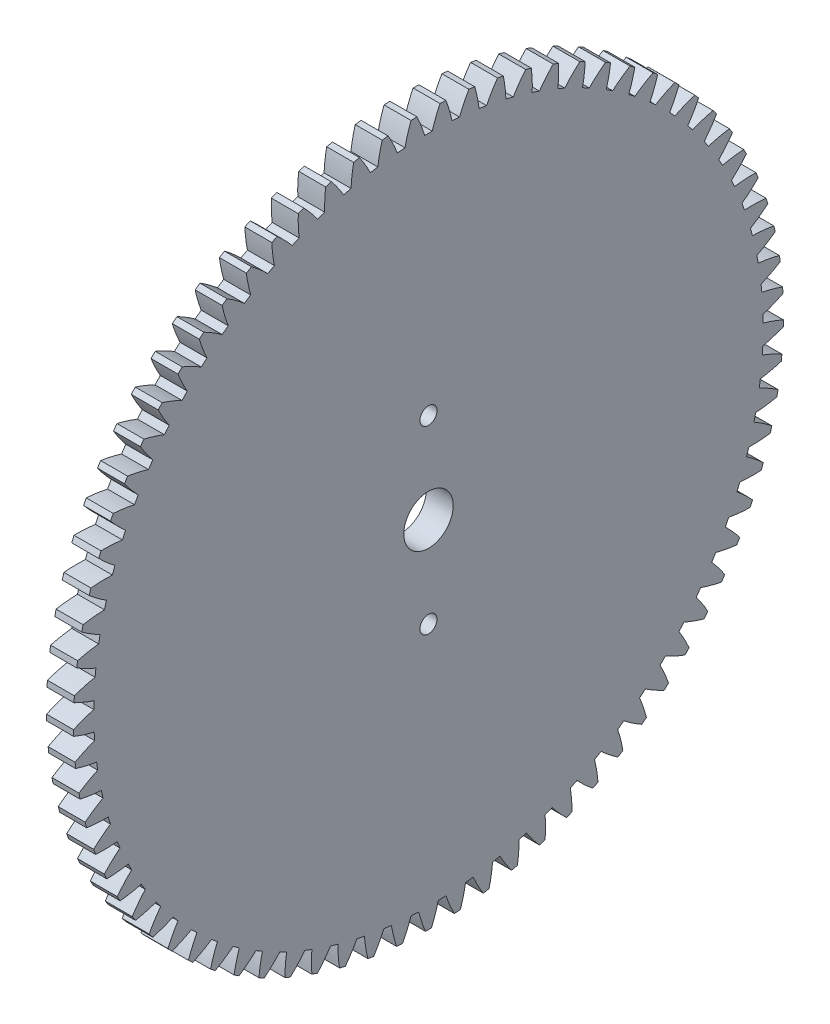
SolidWorks part; units mm, degrees
ref_plane "Plane1" through (0, 0, 0) normal (0, 0, 1) x (1, 0, 0)
ref_plane "Plane2" through (0, 0, 0) normal (0, 1, 0) x (1, 0, 0)
ref_plane "Plane3" through (0, 0, 0) normal (1, 0, 0) x (0, 0, -1)
sketch "HoldingSke" plane through (0, 0, 0) normal (0, 1, 0) x (1, 0, 0)
  line L0 (0, 0) -> (0.225, -0.9744)
  line L1 (-15, 0) -> (100, 0) construction
  line L2 (0, 0) -> (-2.1039, 2.3779)
  line L3 (0, 0) -> (-11.863, 4.5341)
  line L4 (0, 0) -> (1.9427, 8.4147)
  line L5 (0, 0) -> (-46.8476, -17.4728)
  line L6 (0, 0) -> (-1.6579, -1.1186)
  line L7 (-2.1039, 2.3779) -> (8.6586, 51.2059)
  line L8 (-76.2, 54.61) -> (-76.1, 54.61)
  line L9 (-71.009, 38.7566) -> (-53.1078, 45.2721)
  line L10 (-76.2, 71.12) -> (104.1128, 71.12)
  line L11 (0, 0) -> (-2, 0)
  line L12 (-76.2, 101.6) -> (-76.162, 101.6)
  line L13 (24.9733, 27.94) -> (52.9518, 28.4284)
  line L14 (24.9733, 27.94) -> (24.9743, 27.94)
  line L15 (24.9733, 27.94) -> (100.4006, 29.5858)
  line L16 (-63.627, -1) -> (-12.827, -1)
  circle A0 centre (0, 0) radius 0.5
  circle A1 centre (0, 0) radius 37.249
  circle A2 centre (0, 0) radius 37.5
  circle A3 centre (0, 0) radius 0.5
  dimension "MHD" = 74.498
  dimension "Hub_dia" = 75
  dimension "Bore" = 1
  dimension "MBD" = 1
  dimension "Num_teeth" = 77
  dimension "Pitch" = 1
  dimension "Overall_len" = 50
  dimension "Show_teeth" = 77
  dimension "Thickness" = 2
  dimension "OAL" = 50.0001
  dimension "T_dim" = 0.1
  dimension "Ap" = 20
  dimension "H" = 19.05
  dimension "Pitch_radius" = 180.3128
  dimension "Width" = 2
  dimension "Backlash" = 0.038
  dimension "Addendum_fac" = 1
  dimension "Dedendum_fac" = 1.25
  dimension "Clearance_fac" = 0.25
  dimension "Dedendum_add" = 0.001
  dimension "Module" = 1
sketch "BasProSke" plane through (0, 0, 0) normal (0, 1, 0) x (1, 0, 0)
  line L0 (-10, 0) -> (60, 0) construction
  line L1 (0, 0) -> (0, 39.5)
  line L2 (0, 0) -> (2, 0)
  line L3 (2, 0) -> (2, 39.5)
  line L4 (2, 39.5) -> (0, 39.5)
  dimension "Thickness" = 2
  dimension "Diameter" = 79
revolve "Base-Revolve" add sketch "BasProSke" angle 360 about L0
sketch "TooCutSke" plane through (0, 0, 0) normal (1, 0, 0) x (0, 0, -1)
  line L1 (0, 0) -> (0, 107) construction
  line L2 (0, 0) -> (-0.8518, 38.4906) construction
  line L3 (0, 0) -> (-3.1402, 76.9225) construction
  line L4 (-0.8518, 38.4906) -> (-1.5701, 38.4613) construction
  arc A0 (0.4217, 37.2466) -> (-0.4217, 37.2466) centre (0, 0) ccw
  arc A1 (1.2943, 39.5042) -> (-1.2943, 39.5042) centre (0, 0) ccw
  circle A2 centre (0, 0) radius 38.5 construction
  circle A3 centre (0, 0) radius 36.1782 construction
  arc A4 (-0.4217, 37.2466) -> (-1.2943, 39.5042) centre (-15.1779, 32.8404) ccw
  arc A5 (1.2943, 39.5042) -> (0.4217, 37.2466) centre (15.1779, 32.8404) ccw
  dimension "Root_dia" = 74.498
  dimension "Overcut_dia" = 79.0508
  dimension "Pitch_dia" = 77
  dimension "Base_dia" = 72.3563
  dimension "Flank_rad" = 15.4
  dimension "Half_ang" = 2.338
  dimension "Half_CT" = 0.7188
extrude "ToothCut" cut sketch "TooCutSke" along normal through all
fillet "Breaks" [suppressed] radius 0.02 tangent propagation no
fillet "RootFillets" [suppressed] radius 0.251
pattern_circular "TeethCuts" count 77 every 4.675 about axis through (-10, 0, 0) along (1, 0, 0) of "ToothCut", "RootFillets", "Breaks"
sketch "HubNeaOneSke" plane through (0, 0, 0) normal (-1, 0, 0) x (0, 0, 1)
  circle A0 centre (0, 0) radius 37.249
  dimension "Diameter" = 74.498
extrude "HubNearOne" [suppressed] add sketch "HubNeaOneSke" along normal blind 48.0001
sketch "HubNeaBotSke" plane through (0, 0, 0) normal (-1, 0, 0) x (0, 0, 1)
  circle A0 centre (0, 0) radius 37.249
  dimension "Diameter" = 74.498
extrude "HubNearBoth" [suppressed] add sketch "HubNeaBotSke" along normal blind 24
ref_plane "FarPln" through (2, 0, 0) normal (1, 0, 0) x (0, 0, -1)
sketch "HubFarSke" plane through (2, 0, 0) normal (1, 0, 0) x (0, 0, -1)
  circle A0 centre (0, 0) radius 37.249
  dimension "Diameter" = 74.498
extrude "HubFar" [suppressed] add sketch "HubFarSke" along normal blind 24
sketch "BorSke" plane through (0, 0, 0) normal (1, 0, 0) x (0, 0, -1)
  circle A0 centre (0, 0) radius 2.75
  circle A1 centre (0, -10.05) radius 0.95
  circle A2 centre (0, 10.05) radius 0.95
  dimension "Diameter" = 5.5
  dimension "D3" = 1.9
  dimension "D4" = 1.9
  dimension "D1" = 10.05
  dimension "D2" = 10.05
extrude "Bore" cut sketch "BorSke" along normal mid plane 100.0001
sketch "KeySke" plane through (0, 0, 0) normal (1, 0, 0) x (0, 0, -1)
  line L0 (-0.05, 0) -> (-0.05, 0.6)
  line L1 (-0.05, 0.6) -> (0.05, 0.6)
  line L2 (0.05, 0.6) -> (0.05, 0)
  line L3 (0, 0) -> (0, 34) construction
  line L4 (-0.05, 0) -> (0.05, 0)
  dimension "Offset" = 0.6
  dimension "Width" = 0.1
extrude "Keyway" [suppressed] cut sketch "KeySke" along normal mid plane 100.0001
pattern_circular "Keyway2" [suppressed] count 2 every 90 about axis through (-10, 0, 0) along (1, 0, 0) reverse direction yes
scale "Scale1" scale about centroid uniform scaling no x scale factor 1.5 y scale factor 1 z scale factor 1
equation "' \"Module@HoldingSke\" = 6.35"
equation "' \"Num_teeth@HoldingSke\" = 12"
equation "' \"Ap@HoldingSke\" =  20"
equation "' \"Ap@HoldingSke\" = 20"
equation "' \"Width@HoldingSke\" = 0.5 * 25.4"
equation "' \"Hub_dia@HoldingSke\"= 1 * 25.4"
equation "' \"Hub_dia@HoldingSke\" = 1 * 25.4"
equation "' \"Overall_len@HoldingSke\" = 1.0 * 25.4"
equation "' \"Bore@HoldingSke\" = 0.75 * 25.4"
equation "' \"T_dim@HoldingSke\" = 0.1 * 25.4"
equation "' \"Width@KeySke\" = 0.25 * 25.4"
equation "' \"Show_teeth@HoldingSke\" = 13"
equation "' \"Backlash@HoldingSke\" = 0.009 * 25.4"
equation "' \"Addendum_fac@HoldingSke\" = 1.0"
equation "' \"Dedendum_fac@HoldingSke\" = 1.25"
equation "' \"Dedendum_add@HoldingSke\" = 0.00005 * 25.4"
equation "' \"Clearance_fac@HoldingSke\" = 0.25"
equation "\"Pitch@HoldingSke\" = 1 / \"Module@HoldingSke\""
equation "\"Overcut_dia@TooCutSke\" = (\"Num_teeth@HoldingSke\" + 2 * \"Addendum_fac@HoldingSke\") / \"Pitch@HoldingSke\" + 0.002 * 25.4"
equation "\"Pitch_dia@TooCutSke\" = \"Num_teeth@HoldingSke\" / \"Pitch@HoldingSke\""
equation "\"Base_dia@TooCutSke\" = \"Num_teeth@HoldingSke\" / \"Pitch@HoldingSke\" * cos((\"Ap@HoldingSke\"  * 3.14159265 / 180))"
equation "\"Root_dia@TooCutSke\" = (\"Num_teeth@HoldingSke\" + 2) / \"Pitch@HoldingSke\" - 2 * (\"Addendum_fac@HoldingSke\" + \"Dedendum_fac@HoldingSke\") / \"Pitch@HoldingSke\" - \"Dedendum_add@HoldingSke\" * 2"
equation "\"Half_ang@TooCutSke\" = 180 / \"Num_teeth@HoldingSke\""
equation "\"Half_CT@TooCutSke\" = \"Num_teeth@HoldingSke\" / \"Pitch@HoldingSke\" * sin((3.14159265 / 2 / \"Num_teeth@HoldingSke\")) / 2 - 7 * \"Backlash@HoldingSke\" / 4"
equation "\"Flank_rad@TooCutSke\" = \"Num_teeth@HoldingSke\" / \"Pitch@HoldingSke\" / 5"
equation "\"Radius@RootFillets\" = \"Clearance_fac@HoldingSke\" / \"Pitch@HoldingSke\" + \"Dedendum_add@HoldingSke\""
equation "\"Break_rad@Breaks\" = 0.02 / \"Pitch@HoldingSke\""
equation "\"Thickness@HoldingSke\" = \"Width@HoldingSke\""
equation "\"OAL@HoldingSke\" = \"Thickness@HoldingSke\""
equation "\"MHD@HoldingSke\" = (\"Num_teeth@HoldingSke\" + 2) / \"Pitch@HoldingSke\" - 2 * (\"Addendum_fac@HoldingSke\" + \"Dedendum_fac@HoldingSke\")  / \"Pitch@HoldingSke\" - \"Dedendum_add@HoldingSke\" * 2"
equation "\"MBD@HoldingSke\" = (\"Num_teeth@HoldingSke\" + 2) / \"Pitch@HoldingSke\" - 2 * (\"Addendum_fac@HoldingSke\" + \"Dedendum_fac@HoldingSke\")  / \"Pitch@HoldingSke\" - \"Dedendum_add@HoldingSke\" * 2 - 0.002 * 25.4"
equation "\"MHD@HoldingSke\" = ((sgn( \"MHD@HoldingSke\" - \"Hub_dia@HoldingSke\" )-1)*( \"MHD@HoldingSke\" - \"Hub_dia@HoldingSke\" ))/-2+ \"Hub_dia@HoldingSke\""
equation "\"MBD@HoldingSke\" = ((sgn( \"MBD@HoldingSke\" - \"Bore@HoldingSke\" )-1)*( \"MBD@HoldingSke\" - \"Bore@HoldingSke\" ))/-2+ \"Bore@HoldingSke\""
equation "\"OAL@HoldingSke\" = ((sgn( \"OAL@HoldingSke\" - \"Overall_len@HoldingSke\" )+1)*( \"OAL@HoldingSke\" - \"Overall_len@HoldingSke\" ))/2 + \"Overall_len@HoldingSke\" + 0.000002 * 25.4"
equation "\"Num_teeth@TeethCuts\" = int( \"Show_teeth@HoldingSke\" ) + 1"
equation "\"Num_teeth@TeethCuts\" = ((sgn( \"Num_teeth@TeethCuts\" - \"Num_teeth@HoldingSke\" )-1)*( \"Num_teeth@TeethCuts\" - \"Num_teeth@HoldingSke\" ))/-2+ \"Num_teeth@HoldingSke\""
equation "\"Num_teeth@TeethCuts\" = ((sgn( \"Num_teeth@TeethCuts\" - 2.0)+1)*( \"Num_teeth@TeethCuts\" - 2.0))/2 +2.0"
equation "\"Angle@TeethCuts\" = 360.0 / \"Num_teeth@HoldingSke\""
equation "\"Diameter@BasProSke\" = (\"Num_teeth@HoldingSke\" + 2 * \"Addendum_fac@HoldingSke\") / \"Pitch@HoldingSke\""
equation "\"Thickness@BasProSke\"  = \"Thickness@HoldingSke\""
equation "' \"Fillet_rad@BasProSke\" =  \"Thickness@HoldingSke\" * 0.05"
equation "' \"Fillet_rad@BasProSke\" = \"Thickness@HoldingSke\" * 0.05"
equation "\"MHD@HoldingSke\" = ((sgn( \"MHD@HoldingSke\" - \"Root_dia@TooCutSke\" )-1)*( \"MHD@HoldingSke\" - \"Root_dia@TooCutSke\" ))/-2+ \"Root_dia@TooCutSke\""
equation "\"Diameter@HubNeaOneSke\" = \"MHD@HoldingSke\""
equation "\"Length@HubNearOne\" = \"OAL@HoldingSke\" - \"Thickness@BasProSke\""
equation "\"Diameter@HubNeaBotSke\" = \"MHD@HoldingSke\""
equation "\"Length@HubNearBoth\" = ( \"OAL@HoldingSke\" - \"Thickness@BasProSke\" ) / 2.0"
equation "\"Thickness@FarPln\" = \"Thickness@BasProSke\""
equation "\"Diameter@HubFarSke\" = \"MHD@HoldingSke\""
equation "\"Length@HubFar\" = ( \"OAL@HoldingSke\" - \"Thickness@BasProSke\" ) / 2.0"
equation "\"Diameter@BorSke\"=5.5mm"
equation "\"D1@Bore\" = \"OAL@HoldingSke\" * 2.0"
equation "\"D1@Keyway\" = \"OAL@HoldingSke\" * 2.0"
equation "\"Offset@KeySke\" = \"T_dim@HoldingSke\" + \"MBD@HoldingSke\" / 2.0"
